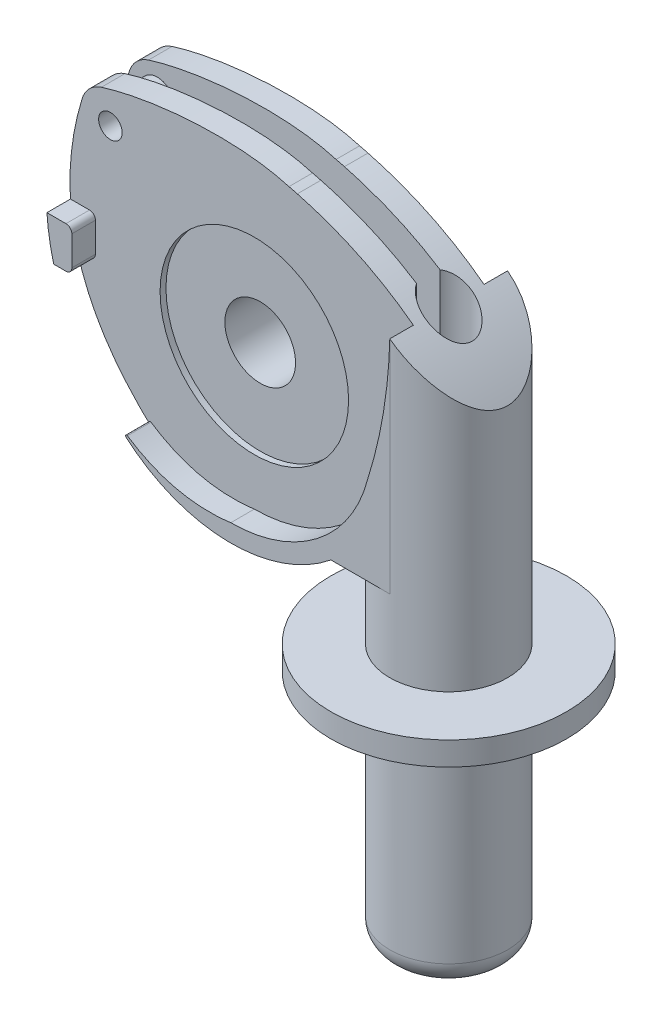
SolidWorks part; units mm, degrees
material "Copper"
ref_plane "Front Plane" through (0, 0, 0) normal (0, 0, 1) x (1, 0, 0)
ref_plane "Top Plane" through (0, 0, 0) normal (0, 1, 0) x (1, 0, 0)
ref_plane "Right Plane" through (0, 0, 0) normal (1, 0, 0) x (0, 0, -1)
sketch "Sketch1" plane through (0, 0, 0) normal (0, 1, 0) x (1, 0, 0)
  circle A0 centre (0, 0) radius 5
extrude "Boss-Extrude1" add sketch "Sketch1" along normal blind 20
sketch "Sketch2" plane through (0, 20, 0) normal (0, 1, 0) x (1, 0, 0)
  circle A0 centre (0, 0) radius 10
extrude "Boss-Extrude2" add sketch "Sketch2" along normal blind 2
sketch "Sketch3" plane through (0, 20, 0) normal (0, -1, 0) x (1, 0, 0)
  circle A0 centre (0, 0) radius 7.5
  circle A1 centre (0, 0) radius 5
extrude "Cut-Extrude1" cut sketch "Sketch3" against normal blind 1
sketch "Sketch4" plane through (0, 22, 0) normal (0, 1, 0) x (1, 0, 0)
  circle A0 centre (0, 0) radius 5
extrude "Boss-Extrude3" add sketch "Sketch4" along normal blind 20
ref_plane "Plane2" through (0, 0, 5) normal (0, 0, 1) x (1, 0, 0)
sketch "Sketch7" plane through (0, 0, 5) normal (0, 0, 1) x (1, 0, 0)
  line L1 (-5, 42) -> (-5, 22) construction
  line L5 (-5, 28.1619) -> (-5, 42)
  line L6 (-5, 42) -> (-0.4223, 42)
  line L7 (5, 42) -> (-5, 42) construction
  arc A0 (-0.4223, 42) -> (-5, 28.1619) centre (-13.5, 38.65) ccw
sketch "Sketch8" plane through (0, 22, 0) normal (0, 1, 0) x (1, 0, 0)
  line L0 (0, -5) -> (-5, -5)
  line L1 (-11, -5) -> (11, -5) construction
  line L2 (-27, -5) -> (-0.4223, -5) construction
  line L3 (-5, -5) -> (-0.4223, -5) construction
  line L4 (-5, -5) -> (-5, 5)
  line L5 (-5, 5) -> (0, 5)
  circle A0 centre (0, 0) radius 5 construction
  circle A1 centre (0, 0) radius 5 construction
  arc A3 (0, 5) -> (0, -5) centre (0, 0) ccw
  circle M2 centre (0, 0) radius 5
extrude "Boss-Extrude10" add sketch "Sketch8" along normal blind 20 contours L4 L0 M2 region at (-3.8832, 22, 3.8832)
mirror "Mirror1" about plane through (0, 0, 0) normal (0, 0, 1) of "Boss-Extrude10"
extrude "Boss-Extrude11" add sketch "Sketch7" against normal blind 10
sketch "Sketch9" plane through (0, 0, 5) normal (0, 0, 1) x (1, 0, 0)
  line L0 (5, 42) -> (-0.4223, 42)
  arc A0 (-0.4223, 42) -> (-5, 28.1619) centre (-13.5, 38.65) ccw construction
  arc A1 (-26.4862, 51.1692) -> (-28.1206, 49.5097) centre (-25.7273, 48.7872) ccw
  arc A2 (-10.5602, 51.826) -> (-22.406, 28.5044) centre (-13.5, 38.65) ccw
  arc A3 (-0.4223, 42) -> (-22.406, 28.5044) centre (-13.5, 38.65) ccw
  spline S1 degree 3 poles (-10.5602, 51.826) (-14.9561, 53.1458) (-22.2177, 52.5291) (-26.4862, 51.1692) knots 0 0 0 0 0.912268 0.912268 0.912268 0.912268
  spline S2 degree 3 poles (-28.1206, 49.5097) (-30.5712, 41.392) (-28.6326, 34.2662) (-22.406, 28.5044) knots 0.048079 0.048079 0.048079 0.048079 1 1 1 1
  dimension "D1" = 2.5
extrude "Boss-Extrude12" add sketch "Sketch9" against normal blind 10 contours A1 S2 A3 S1 region at (-25.161, 46.3045, 5)
sketch "Sketch10" plane through (0, 0, 5) normal (0, 0, 1) x (1, 0, 0)
  line L0 (5, 42) -> (-0.4223, 42)
  arc A0 (-0.4223, 42) -> (-10.5602, 51.826) centre (-13.5, 38.65) ccw
  spline S0 degree 2 poles (5, 42) (-0.9689, 49.5261) (-10.5602, 51.826) knots 0 0 0 1 1 1
  line M4 (0, 42) -> (-0.4223, 42)
  arc M5 (-0.4223, 42) -> (-10.5602, 51.826) centre (-13.5, 38.65) ccw
extrude "Boss-Extrude13" add sketch "Sketch10" against normal blind 10 contours L0 S0 M5 M4 region at (-0.2317, 45.2726, 5)
sketch "Sketch11" plane through (0, 42, 0) normal (0, -1, 0) x (1, 0, 0)
  line L0 (5, 0) -> (5, 5)
  line L1 (5, 5) -> (0, 5)
  line L2 (5, 0) -> (5, -5)
  line L3 (5, -5) -> (0, -5)
  arc A0 (0, -5) -> (0, 5) centre (0, 0) ccw
  line M1 (5, 5) -> (0, 5)
  arc M2 (0, 5) -> (5, 0) centre (0, 0) cw
  line M3 (5, 0) -> (5, 5)
extrude "Cut-Extrude2" cut sketch "Sketch11" against normal blind 10 contours M3 M1 M2 | A0 L3 L2 region at (3.8832, 42, 3.8832) region at (3.8832, 42, -3.8832)
sketch "Sketch12" plane through (0, 0, 5) normal (0, 0, 1) x (1, 0, 0)
  arc A0 (-13.5, 26.65) -> (-1.8787, 35.659) centre (-13.5, 38.65) ccw
  spline S0 degree 2 poles (0, 46.9202) (-0.1477, 41.1653) (-1.8787, 35.659) knots 0 0 0 1 1 1
  spline S1 degree 2 poles (-13.5, 26.65) (-19.0129, 25.9326) (-23.4256, 29.4994) knots 0 0 0 1 1 1
  spline S2 degree 3 poles (-23.4256, 29.4994) (-34.1861, 28.6537) (-40.5715, 57.0896) (-14.7475, 54.3638) (-4.0927, 55.6999) (0, 46.9202) knots 0 0 0 0 0.449067 0.671266 1 1 1 1
  dimension "D1" = 24
extrude "Cut-Extrude3" cut sketch "Sketch12" against normal blind 2
mirror "Mirror2" about plane through (0, 0, 0) normal (0, 0, 1) of "Cut-Extrude3"
sketch "Sketch14" plane through (0, 22, 0) normal (0, 1, 0) x (1, 0, 0)
  line L0 (0, -5) -> (-5, -5)
  line L1 (-27, -5) -> (-0.4223, -5) construction
  line L2 (-5, -5) -> (-5, 0)
  arc A0 (-5, 0) -> (0, -5) centre (0, 0) ccw
extrude "Cut-Extrude5" cut sketch "Sketch14" along normal up to vertex up to point (-5, 28.1619, 5)
sketch "Sketch16" plane through (0, 22, 0) normal (0, 1, 0) x (1, 0, 0)
  line L0 (0, 5) -> (-5, 5)
  line L1 (-5, 5) -> (-5, 0)
  arc A0 (0, 5) -> (-5, 0) centre (0, 0) ccw
extrude "Cut-Extrude6" cut sketch "Sketch16" along normal up to vertex up to point (-5, 28.1619, -5)
sketch "Sketch17" plane through (0, 0, -3) normal (0, 0, -1) x (-1, 0, 0)
  circle A0 centre (13.5, 38.65) radius 8
  dimension "D1" = 16
extrude "Cut-Extrude7" cut sketch "Sketch17" against normal blind 0.5
mirror "Mirror5" about plane through (0, 0, 0) normal (0, 0, 1) of "Cut-Extrude7"
sketch "Sketch18" plane through (0, 0, -2.5) normal (0, 0, -1) x (-1, 0, 0)
  circle A0 centre (13.5, 38.65) radius 3
extrude "Cut-Extrude8" cut sketch "Sketch18" against normal blind 22.5
fillet "Fillet3" radius 0.1 2 edges
sketch "Sketch20" plane through (0, 0, -2.5) normal (0, 0, -1) x (-1, 0, 0)
  line L0 (0, 38.65) -> (0, 51.826)
  line L1 (0, 51.826) -> (10.5602, 51.826)
  line L2 (0, 38.65) -> (0, 22)
  line L3 (10, 22) -> (-10, 22) construction
  line L4 (0, 22) -> (5, 22)
  line L5 (5, 22) -> (5, 28.1619)
  arc A0 (5, 28.1619) -> (22.3974, 28.4969) centre (13.5, 38.65) ccw
  circle A1 centre (13.5, 38.65) radius 3.5
  spline S0 degree 3 poles (10.5602, 51.826) (20.353, 65.3664) (55.4967, 41.0552) (22.3974, 28.4969) knots 0 0 0 0 1 1 1 1
extrude "Cut-Extrude12" cut sketch "Sketch20" against normal blind 2 from offset 1.5 offset against normal yes
sketch "Sketch21" plane through (0, 22, 0) normal (0, 1, 0) x (1, 0, 0)
  circle A0 centre (0, 0) radius 2
extrude "Cut-Extrude13" cut sketch "Sketch21" along normal through all and the other way blind 10
sketch "Sketch22" plane through (0, 0, -3) normal (0, 0, -1) x (-1, 0, 0)
  line L0 (28.5222, 38.1418) -> (26.9904, 38.1415)
  line L1 (26.9904, 38.1415) -> (26.9899, 41.6415)
  line L2 (26.9899, 41.6415) -> (29.1057, 41.6415)
  arc A1 (22.406, 28.5044) -> (10.5602, 51.826) centre (13.5, 38.65) ccw construction
  parabola Q0 (22.2763, 28.6554) -> (13.5, 26.65) focus (16.9121, 32.7476) apex (18.41, 26.9145) construction
  parabola Q1 (22.2763, 28.6554) -> (13.5, 26.65) focus (16.9121, 32.7476) apex (18.41, 26.9145) construction
  spline S0 degree 3 poles (13.5, 26.65) (16.509, 26.2085) (23.8699, 27.8046) (27.3716, 34.6533) (28.5222, 38.1418) knots 0 0 0 0 0.443253 1 1 1 1
  spline S1 degree 3 poles (28.1206, 49.5097) (30.5712, 41.392) (28.6326, 34.2662) (22.406, 28.5044) knots 0.048079 0.048079 0.048079 0.048079 1 1 1 1 construction
  spline S2 degree 3 poles (28.1206, 49.5097) (30.432, 41.8531) (28.8387, 35.0789) (23.4256, 29.4994) knots 0.048079 0.048079 0.048079 0.048079 0.945927 0.945927 0.945927 0.945927 construction
  spline S3 degree 2 poles (29.1057, 41.6415) (28.9866, 39.8662) (28.5222, 38.1418) knots 0 0 0 1 1 1
  spline M14 degree 3 poles (28.1206, 49.5097) (30.5712, 41.392) (28.6326, 34.2662) (22.406, 28.5044) knots 0.048079 0.048079 0.048079 0.048079 1 1 1 1 only from (23.4256, 29.4994) to (28.1206, 49.5097)
  dimension "D1" = 3.5
extrude "Boss-Extrude14" add sketch "Sketch22" along normal blind 2 contours S3 L2 L1 L0 M14 region at (-27.9392, 39.9819, -3)
fillet "Fillet4" radius 0.5 2 edges at (-26.9904, 38.1415, -4) (-26.9899, 41.6415, -4)
mirror "Mirror6" about plane through (0, 0, 0) normal (0, 0, 1) of "Boss-Extrude14", "Fillet4"
sketch "Sketch23" plane through (0, 0, 0) normal (0, -1, 0) x (1, 0, 0)
  circle A0 centre (0, 0) radius 3
extrude "Cut-Extrude14" cut sketch "Sketch23" against normal blind 20
cosmetic thread "Cosmetic Thread3" parameters "D2"=8
sketch "Sketch24" plane through (0, 0, 3) normal (0, 0, 1) x (1, 0, 0)
  circle A0 centre (-25.7175, 48.7054) radius 1
  dimension "D1" = 2
extrude "Cut-Extrude15" cut sketch "Sketch24" against normal blind 10
sketch "Sketch25" plane through (0, 0, 1) normal (0, 0, -1) x (-1, 0, 0)
  circle A0 centre (25.7273, 48.7872) radius 1.5
  circle A1 centre (25.7273, 48.7872) radius 1
extrude "Boss-Extrude15" add sketch "Sketch25" along normal blind 2
fillet "Fillet5" radius 2 1 edges at (0, 0, 5)
